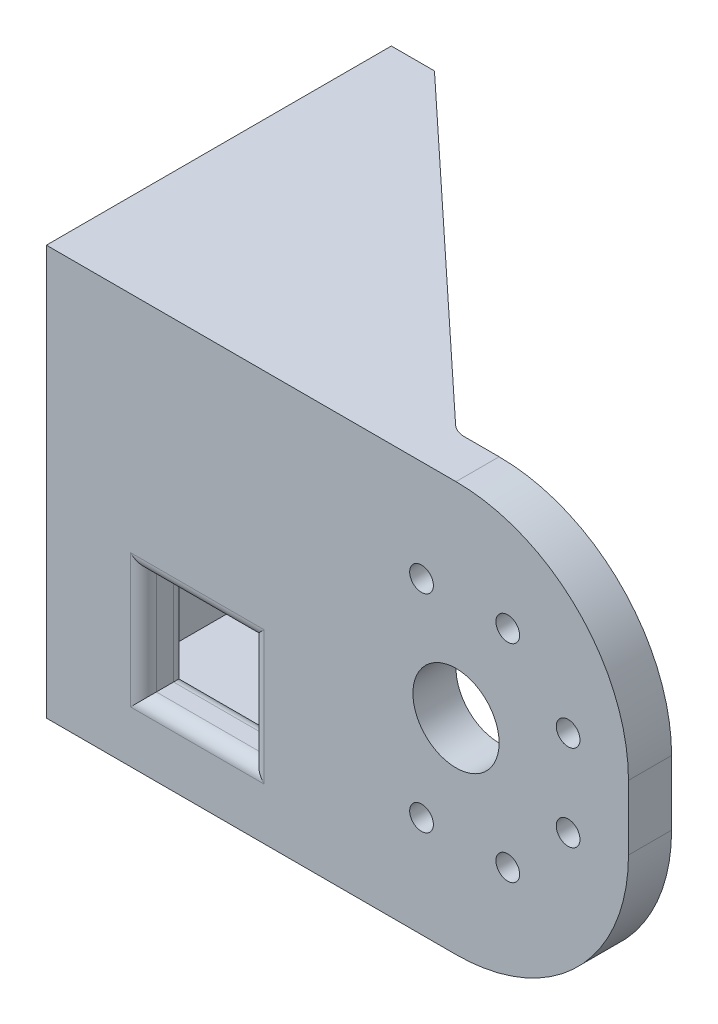
SolidWorks part; units mm, degrees
ref_plane "Front Plane" through (0, 0, 0) normal (0, 0, 1) x (1, 0, 0)
ref_plane "Top Plane" through (0, 0, 0) normal (0, 1, 0) x (1, 0, 0)
ref_plane "Right Plane" through (0, 0, 0) normal (1, 0, 0) x (0, 0, -1)
sketch "Sketch3" plane through (0, 0, 0) normal (0, 0, 1) x (1, 0, 0)
  line L6 (68.6171, 80.0599) -> (163.6171, 80.0599)
  line L10 (68.6171, 80.0599) -> (68.6171, -14.9401)
  line L36 (-101.4371, 49.8561) -> (-17.2351, 49.8561) construction
  line L70 (68.6171, -14.9401) -> (163.6171, -14.9401)
  line L71 (203.6171, 40.0599) -> (203.6171, 25.0599)
  circle A22 centre (163.6171, 32.5599) radius 10
  circle A23 centre (189.6171, 42.5599) radius 2.75
  circle A24 centre (155.6171, 56.5599) radius 2.75
  circle A25 centre (175.6171, 56.5599) radius 2.75
  circle A26 centre (155.6171, 8.5599) radius 2.75
  circle A27 centre (175.6171, 8.5599) radius 2.75
  circle A28 centre (189.6171, 22.5599) radius 2.75
  arc A29 (163.6171, -14.9401) -> (203.6171, 25.0599) centre (163.6171, 25.0599) ccw
  arc A30 (163.6171, 80.0599) -> (203.6171, 40.0599) centre (163.6171, 40.0599) cw
  point P23 (203.6171, 80.0599)
  dimension "D3" = 10
  dimension "D4" = 26
  dimension "D7" = 5.5
  dimension "D21" = 135
  dimension "D22" = 40
  dimension "D23" = 47.5
  dimension "D1" = 20
  dimension "D24" = 40
  dimension "D10" = 8
  dimension "D11" = 24
  dimension "D12" = 20
  dimension "D15" = 20
  dimension "D16" = 8
  dimension "D17" = 20
  dimension "D18" = 48
  dimension "D19" = 48
  dimension "D20" = 95
  dimension "D13" = 26
  dimension "D14" = 24
extrude "Boss-Extrude1" add sketch "Sketch3" along normal blind 10
sketch "Sketch4" plane through (0, 0, 0) normal (0, 0, -1) x (-1, 0, 0)
  line L0 (-68.6171, -14.9401) -> (-163.6171, -14.9401) construction
  line L1 (-68.6171, 80.0599) -> (-78.6171, 80.0599)
  line L2 (-68.6171, 80.0599) -> (-68.6171, -14.9401)
  line L3 (-68.6171, -14.9401) -> (-78.6171, -14.9401)
  line L4 (-78.6171, 80.0599) -> (-78.6171, -14.9401)
  dimension "D1" = 10
extrude "Boss-Extrude2" add sketch "Sketch4" along normal blind 70
sketch "Sketch8" plane through (68.6171, 0, 0) normal (-1, 0, 0) x (0, 0, 1)
  line L0 (10, 80.0599) -> (-70, 80.0599) construction
  line L1 (-40, 32.5599) -> (-56.1679, 25.863) construction
  line L2 (-70, 32.5599) -> (0, 32.5599) construction
  line L3 (-70, -14.9401) -> (-70, 80.0599) construction
  circle A0 centre (-40, 32.5599) radius 10
  circle A1 centre (-56.1679, 25.863) radius 2.75
  circle A2 centre (-56.1679, 39.2569) radius 2.75
  circle A3 centre (-46.697, 48.7278) radius 2.75
  circle A4 centre (-33.303, 48.7278) radius 2.75
  circle A5 centre (-23.8321, 39.2569) radius 2.75
  circle A6 centre (-23.8321, 25.863) radius 2.75
  circle A7 centre (-33.303, 16.392) radius 2.75
  circle A8 centre (-46.697, 16.392) radius 2.75
  point P27 (-40, 32.5599)
  dimension "D1" = 20
  dimension "D6" = 5.5
  dimension "D2" = 47.5
  dimension "D3" = 30
  dimension "D4" = 17.5
  dimension "D5" = 22.5
  dimension "D7" = 8
extrude "Cut-Extrude2" cut sketch "Sketch8" against normal blind 43.8
sketch "Sketch9" plane through (0, -14.9401, 0) normal (0, -1, 0) x (1, 0, 0)
  line L0 (78.6171, -70) -> (153.6171, 0)
  line L1 (52.25, 0) -> (-52.25, 0) construction
  line L2 (78.6171, 0) -> (163.6171, 0) construction
  line L3 (78.6171, -70) -> (78.6171, 0)
  line L4 (78.6171, 0) -> (153.6171, 0)
extrude "Boss-Extrude3" add sketch "Sketch9" against normal blind 10
ref_plane "Plane1" through (0, 32.5599, 0) normal (0, -1, 0) x (-1, 0, 0)
mirror "Mirror1" about plane through (0, 32.5599, 0) normal (0, -1, 0) of "Boss-Extrude3"
fillet "Fillet1" radius 5 2 edges at (153.6171, 75.0599, 0) (153.6171, -9.9401, 0)
sketch "Sketch11" plane through (0, 0, 0) normal (0, 0, -1) x (-1, 0, 0)
  line L0 (-78.6171, 70.0599) -> (-78.6171, -4.9401) construction
  line L1 (-91.1171, 0.0599) -> (-116.1171, 0.0599)
  line L2 (-91.1171, 0.0599) -> (-91.1171, 25.0599)
  line L3 (-91.1171, 25.0599) -> (-116.1171, 25.0599)
  line L4 (-116.1171, 0.0599) -> (-116.1171, 25.0599)
  line L5 (-155.5879, -4.9401) -> (-78.6171, -4.9401) construction
  dimension "D1" = 12.5
  dimension "D2" = 25
  dimension "D3" = 25
  dimension "D4" = 5
extrude "Cut-Extrude3" cut sketch "Sketch11" against normal through all
fillet "Fillet3" radius 3 8 edges at (116.1171, 12.5599, 0) (116.1171, 12.5599, 10) (103.6171, 0.0599, 10) (103.6171, 0.0599, 0) (91.1171, 12.5599, 10) (103.6171, 25.0599, 10) (103.6171, 25.0599, 0) (91.1171, 12.5599, 0)
